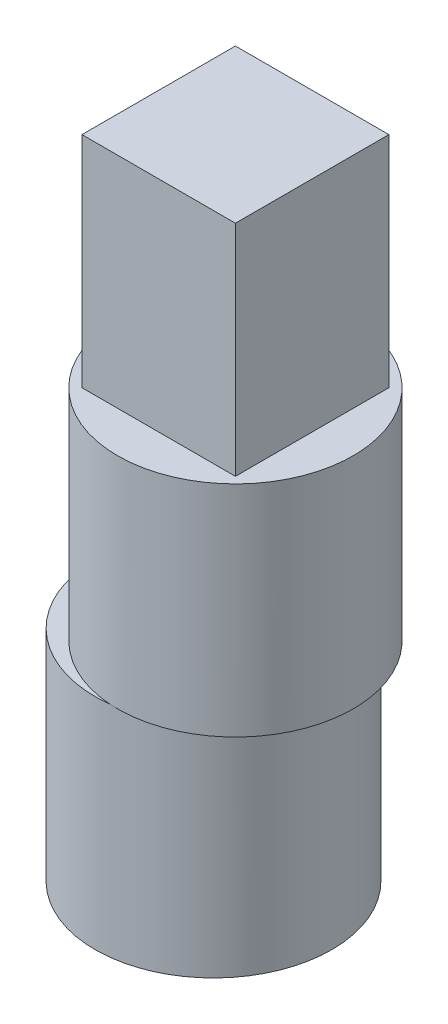
SolidWorks part; units mm, degrees
ref_plane "Ebene vorne" through (0, 0, 0) normal (0, 0, 1) x (1, 0, 0)
ref_plane "Ebene oben" through (0, 0, 0) normal (0, 1, 0) x (1, 0, 0)
ref_plane "Ebene rechts" through (0, 0, 0) normal (1, 0, 0) x (0, 0, -1)
sketch "Skizze1" plane through (0, 0, 0) normal (0, 1, 0) x (1, 0, 0)
  circle A0 centre (0, 0) radius 5.375
  dimension "D1" = 10.75
extrude "Aufsatz-Linear austragen1" add sketch "Skizze1" along normal blind 10
sketch "Skizze2" plane through (0, 0, 0) normal (0, -1, 0) x (-1, 0, 0)
  line L0 (1, -5.2812) -> (1, 5.2812)
  line L1 (-5.375, 0) -> (5.375, 0)
  circle A0 centre (0, 0) radius 5.375 construction
  dimension "D1" = 0
  dimension "D2" = 1
sketch "Skizze3" plane through (0, 0, 0) normal (0, -1, 0) x (-1, 0, 0)
  line L0 (1, -5.2812) -> (1, 5.2812) construction
  line L1 (-5.375, 0) -> (5.375, 0) construction
  circle A0 centre (1, 0) radius 5.4
  point P0 (1, 0)
  dimension "D1" = 10.8
ref_axis "Achse1" through (0, 10, 0) along (0, -1, 0)
extrude "Aufsatz-Linear austragen3" add sketch "Skizze3" along normal blind 10
sketch "Skizze4" plane through (0, 10, 0) normal (0, 1, 0) x (1, 0, 0)
  line L1 (-3.5, 3.5) -> (3.5, 3.5)
  line L2 (-3.5, 3.5) -> (-3.5, -3.5)
  line L3 (-3.5, -3.5) -> (3.5, -3.5)
  line L4 (3.5, 3.5) -> (3.5, -3.5)
  dimension "D1" = 7
  dimension "D2" = 7
  dimension "D3" = 3.5
  dimension "D4" = 3.5
extrude "Aufsatz-Linear austragen4" add sketch "Skizze4" along normal blind 10
